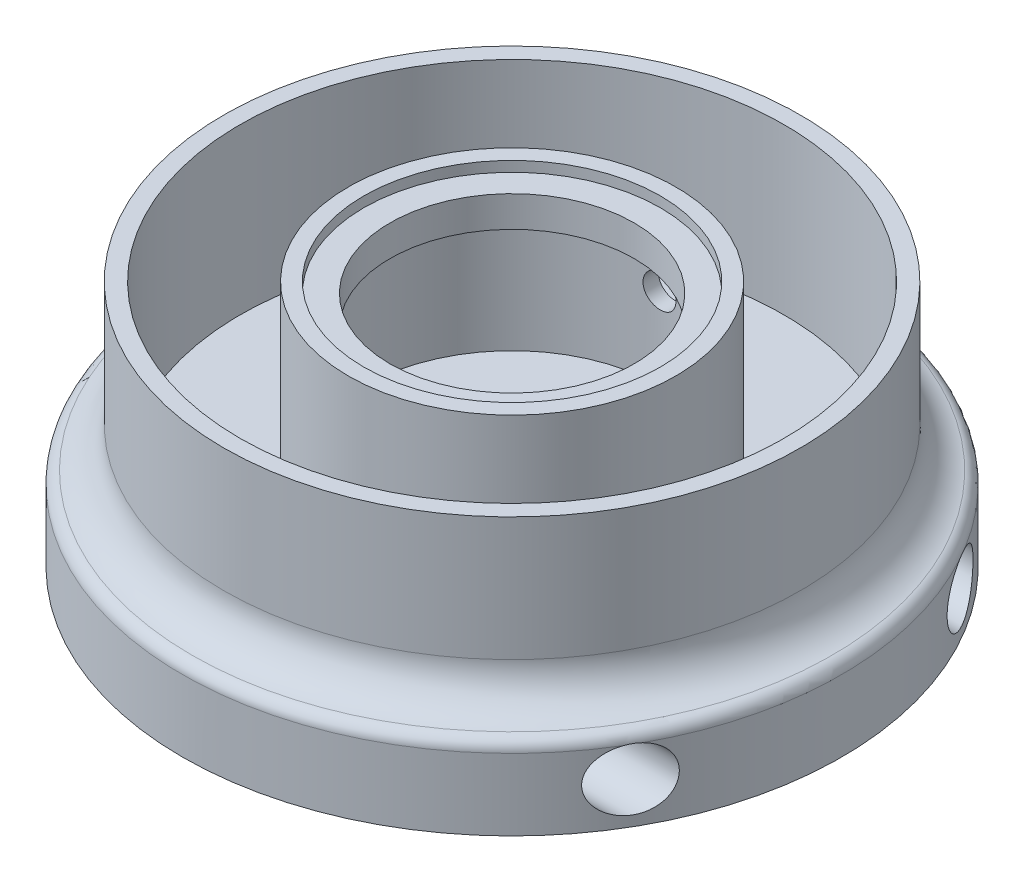
SolidWorks part; units mm, degrees
ref_plane "Front Plane" through (0, 0, 0) normal (0, 0, 1) x (1, 0, 0)
ref_plane "Top Plane" through (0, 0, 0) normal (0, 1, 0) x (1, 0, 0)
ref_plane "Right Plane" through (0, 0, 0) normal (1, 0, 0) x (0, 0, -1)
sketch "Sketch1" plane through (0, 0, 0) normal (0, 1, 0) x (1, 0, 0)
  circle A0 centre (0, 0) radius 101.6
  dimension "D1" = 203.2
extrude "Boss-Extrude1" add sketch "Sketch1" along normal blind 25.4
sketch "Sketch2" plane through (0, 0, 0) normal (1, 0, 0) x (0, 0, -1)
  line L0 (0, 0) -> (0, 19.5505) construction
  circle A1 centre (50.8, 12.7) radius 9.525
  circle A2 centre (-50.8, 12.7) radius 9.525
  dimension "D1" = 12.7
  dimension "D2" = 50.8
sketch "Sketch4" plane through (0, 25.4, 0) normal (0, 1, 0) x (1, 0, 0)
  circle A0 centre (0, 0) radius 88.9
  circle A1 centre (0, 0) radius 83.82
  dimension "D1" = 177.8
  dimension "D2" = 167.64
extrude "Boss-Extrude2" add sketch "Sketch4" along normal blind 50.8
extrude "Cut-Extrude4" cut sketch "Sketch2" against normal blind 101.6 and the other way blind 101.6
fillet "Fillet7" radius 12.7 1 edges at (0, 25.4, 88.9)
fillet "Fillet8" radius 3.81 1 edges at (0, 25.4, 101.6)
sketch "Sketch11" plane through (0, 25.4, 0) normal (0, 1, 0) x (1, 0, 0)
  circle A1 centre (0, 0) radius 50.4825
  circle A2 centre (0, 0) radius 45.72
  circle A3 centre (0, 0) radius 45.72
  dimension "D1" = 38.1
  dimension "D2" = 4.7625
extrude "Boss-Extrude5" add sketch "Sketch11" along normal blind 50.8
sketch "Sketch13" plane through (0, 0, 0) normal (0, 0, 1) x (1, 0, 0)
  line L0 (45.72, 63.5) -> (37.6512, 63.5)
  line L1 (45.72, 25.4) -> (45.72, 76.2) construction
  line L2 (37.6512, 63.5) -> (37.6512, 73.025)
  line L3 (37.6512, 73.025) -> (45.72, 73.025)
  line L4 (45.72, 73.025) -> (45.72, 63.5)
  dimension "D1" = 9.525
ref_axis "Axis2" through (0, 80.01, 0) along (0, -1, 0)
revolve "Revolve1" add sketch "Sketch13" angle 360 about axis through (0, 80.01, 0) along (0, -1, 0)
sketch "Sketch14" plane through (0, 0, 0) normal (0, 0, 1) x (1, 0, 0)
  circle A0 centre (0, 50.8) radius 5.08
  point P2 (0, 0)
extrude "Cut-Extrude5" cut sketch "Sketch14" against normal blind 50.8 contours A0
